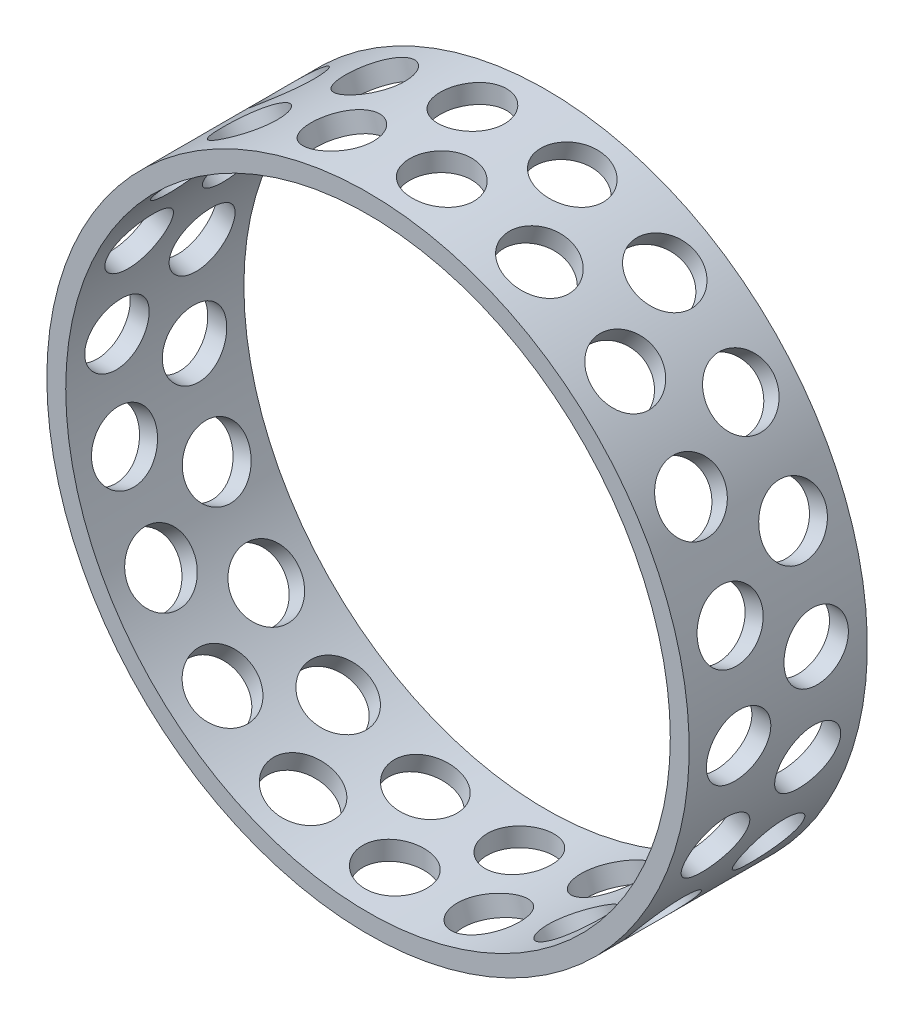
SolidWorks part; units mm, degrees
ref_plane "Front Plane" through (0, 0, 0) normal (0, 0, 1) x (1, 0, 0)
ref_plane "Top Plane" through (0, 0, 0) normal (0, 1, 0) x (1, 0, 0)
ref_plane "Right Plane" through (0, 0, 0) normal (1, 0, 0) x (0, 0, -1)
sketch "Sketch1" plane through (0, 0, 0) normal (1, 0, 0) x (0, 0, -1)
  line L0 (1, 84.9998) -> (48.15, 84.9998)
  line L1 (48.15, 84.9998) -> (48.15, 79.9998)
  line L2 (48.15, 79.9998) -> (1, 79.9998)
  line L3 (1, 79.9998) -> (1, 84.9998)
  dimension "D1" = 84.9998
  dimension "D2" = 5
  dimension "D3" = 47.15
  dimension "D4" = 1
ref_axis "Axis1" through (0, 0, -50.5075) along (0, 0, 1)
revolve "Revolve1" add sketch "Sketch1" angle 360 about axis through (0, 0, -50.5075) along (0, 0, 1)
sketch "Sketch2" plane through (0, 0, 0) normal (1, 0, 0) x (0, 0, -1)
  line L0 (14.3098, 6.2149) -> (24.575, 0) construction
  line L1 (50.5075, 0) -> (-1.3575, 0) construction
  line L2 (24.575, 0) -> (34.8402, -6.2149) construction
  line L3 (1, 84.9998) -> (1, -84.9998) construction
  circle A0 centre (14.3098, 6.2149) radius 8.5
  circle A1 centre (34.8402, -6.2149) radius 8.5
  point P9 (24.8402, 0)
  point P10 (0, 0)
  dimension "D1" = 17
  dimension "D2" = 12
  dimension "D3" = 23.575
extrude "Cut-Extrude1" cut sketch "Sketch2" against normal through all
pattern_circular "CirPattern1" count 20 over 360 about axis through (0, 0, -50.5075) along (0, 0, 1) of "Cut-Extrude1"
